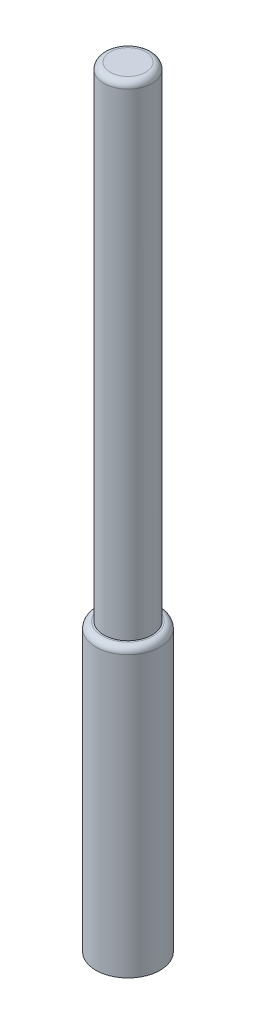
SolidWorks part; units mm, degrees
material "Galvanized Steel"
ref_plane "Front Plane" through (0, 0, 0) normal (0, 0, 1) x (1, 0, 0)
ref_plane "Top Plane" through (0, 0, 0) normal (0, 1, 0) x (1, 0, 0)
ref_plane "Right Plane" through (0, 0, 0) normal (1, 0, 0) x (0, 0, -1)
sketch "Sketch1" plane through (0, 0, 0) normal (0, 1, 0) x (1, 0, 0)
  circle A0 centre (0, 0) radius 6.35
  circle A1 centre (0, 0) radius 4.7625
extrude "Boss-Extrude1" add sketch "Sketch1" along normal blind 56.642 contours A1 | A0
extrude "Boss-Extrude2" add sketch "Sketch1<3>" along normal blind 152.4 contours A1 region at (0, 0, 0)
sketch "Sketch1<3>" plane through (0, 0, 0) normal (0, 1, 0) x (1, 0, 0) same geometry as "Sketch1"
fillet "Fillet1" radius 1.27 2 edges at (0, 56.642, 6.35) (0, 152.4, 4.7625)
sketch "Sketch2" plane through (0, 152.4, 0) normal (0, 1, 0) x (1, 0, 0)
  point P0 (0, 0)
